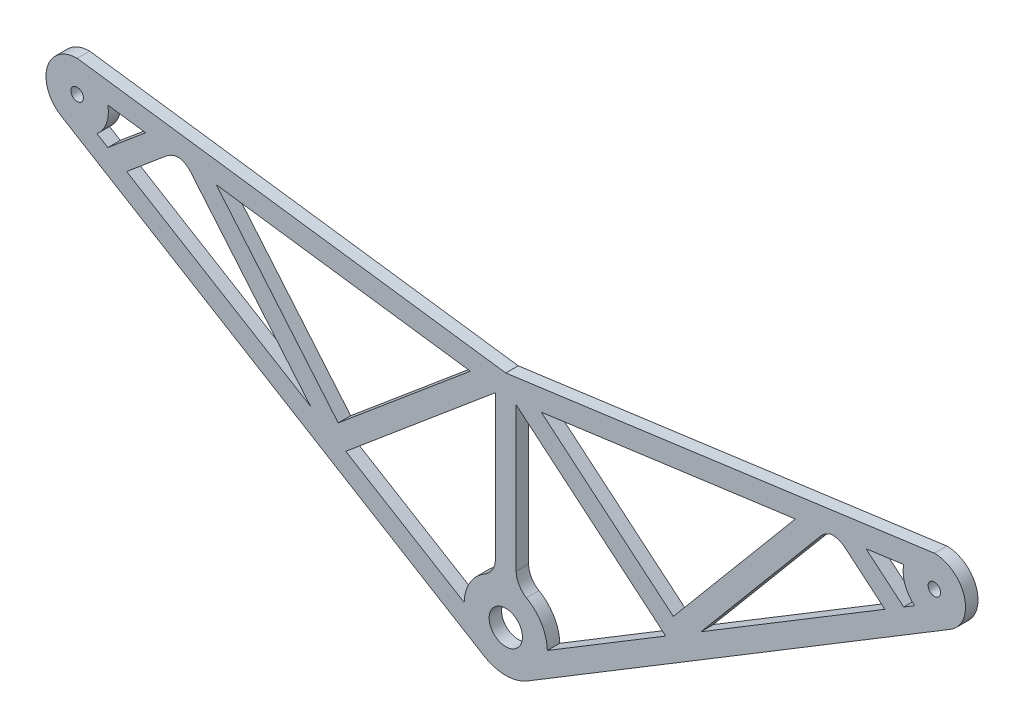
SolidWorks part; units mm, degrees
ref_plane "前视基准面" through (0, 0, 0) normal (0, 0, 1) x (1, 0, 0)
ref_plane "上视基准面" through (0, 0, 0) normal (0, 1, 0) x (1, 0, 0)
ref_plane "右视基准面" through (0, 0, 0) normal (1, 0, 0) x (0, 0, -1)
sketch "草图1" plane through (0, 0, 0) normal (0, 0, 1) x (1, 0, 0)
  line L0 (0, 53) -> (0, -10) construction
  line L1 (0, 0) -> (103.057, 59.5) construction
  line L2 (0, 53) -> (-103.057, 67)
  line L3 (0, 0) -> (-103.057, 59.5) construction
  line L4 (0, 53) -> (103.057, 67)
  line L5 (-106.9426, 53.085) -> (-5.1808, -8.5533)
  line L6 (5.1808, -8.5533) -> (106.9426, 53.085)
  line L7 (0, 53) -> (-40.6004, 18.9323) construction
  line L8 (0, 53) -> (40.6004, 18.9323) construction
  line L9 (-40.6004, 18.9323) -> (-78.0878, 63.608) construction
  line L10 (40.6004, 18.9323) -> (78.0878, 63.608) construction
  line L11 (-78.0878, 63.608) -> (-93.1067, 51.0056) construction
  line L12 (78.0878, 63.608) -> (93.1067, 51.0056) construction
  line L13 (-8.523, 49.1119) -> (-69.6256, 57.4125)
  line L14 (46.9198, 22.5742) -> (91.1632, 49.3729)
  line L15 (-98.3041, 53.6983) -> (-95.6807, 52.1092)
  line L16 (9.9978, 0.2101) -> (38.4702, 17.4562)
  line L17 (-8.523, 49.1119) -> (-40.2922, 22.4543)
  line L18 (-40.2922, 22.4543) -> (-69.6256, 57.4125)
  line L19 (-86.6107, 59.7199) -> (-95.6807, 52.1092)
  line L20 (-2.5, 47.6387) -> (-38.4702, 17.4562)
  line L21 (-46.9198, 22.5742) -> (-76.9924, 58.4133)
  line L22 (-79.916, 58.8104) -> (-91.1632, 49.3729)
  line L23 (2.5, 47.6387) -> (38.4702, 17.4562)
  line L24 (46.9198, 22.5742) -> (76.9924, 58.4133)
  line L25 (79.916, 58.8104) -> (91.1632, 49.3729)
  line L26 (8.523, 49.1119) -> (40.2922, 22.4543)
  line L27 (40.2922, 22.4543) -> (69.6256, 57.4125)
  line L28 (86.6107, 59.7199) -> (95.6807, 52.1092)
  line L29 (-38.4702, 17.4562) -> (-9.9978, 0.2101)
  line L30 (-2.5, 47.6387) -> (-2.5, 9.6825)
  line L31 (2.5, 47.6387) -> (2.5, 9.6825)
  line L32 (77.7796, 67.1301) -> (94.7136, 52.9207) construction
  line L33 (-1.607, 54.9151) -> (-40.2922, 22.4543) construction
  line L34 (1.607, 54.9151) -> (40.2922, 22.4543) construction
  line L35 (1.607, 51.0849) -> (-40.9085, 15.4102) construction
  line L36 (-1.607, 51.0849) -> (40.9085, 15.4102) construction
  line L37 (-2.5, 53) -> (-2.5, -10) construction
  line L38 (2.5, 53) -> (2.5, -10) construction
  line L39 (-40.2922, 22.4543) -> (-77.7796, 67.1301) construction
  line L40 (-77.7796, 67.1301) -> (-94.7136, 52.9207) construction
  line L41 (-40.9085, 15.4102) -> (-78.3959, 60.0859) construction
  line L42 (-78.3959, 60.0859) -> (-91.4997, 49.0905) construction
  line L43 (40.9085, 15.4102) -> (78.3959, 60.0859) construction
  line L44 (2.5, -9.6825) -> (2.5, -10)
  line L45 (40.2922, 22.4543) -> (77.7796, 67.1301) construction
  line L46 (78.3959, 60.0859) -> (91.4997, 49.0905) construction
  line L47 (-2.5, -9.6825) -> (-2.5, -10)
  line L49 (-104.3522, 57.3617) -> (-2.5904, -4.2767) construction
  line L50 (2.5904, -4.2767) -> (104.3522, 57.3617) construction
  line L51 (86.6107, 59.7199) -> (95.6994, 60.9546)
  line L52 (95.6807, 52.1092) -> (98.3041, 53.6983)
  line L53 (76.9924, 58.4133) -> (79.916, 58.8104)
  line L54 (8.523, 49.1119) -> (69.6256, 57.4125)
  line L55 (-76.9924, 58.4133) -> (-79.916, 58.8104)
  line L56 (-86.6107, 59.7199) -> (-95.6994, 60.9546)
  line L57 (-91.1632, 49.3729) -> (-46.9198, 22.5742)
  arc A0 (-2.5, 9.6825) -> (-9.9978, 0.2101) centre (0, 0) ccw
  arc A1 (-98.3041, 53.6983) -> (-95.6994, 60.9546) centre (-103.057, 59.5) ccw
  arc A2 (106.9426, 53.085) -> (101.0562, 66.7282) centre (103.057, 59.5) ccw
  circle A3 centre (0, 0) radius 4
  circle A4 centre (-103.057, 59.5) radius 1.5
  circle A5 centre (103.057, 59.5) radius 1.5
  arc A6 (-5.1808, -8.5533) -> (5.1808, -8.5533) centre (0, 0) ccw
  arc A7 (9.9978, 0.2101) -> (2.5, 9.6825) centre (0, 0) ccw
  arc A8 (95.6994, 60.9546) -> (98.3041, 53.6983) centre (103.057, 59.5) ccw
  arc A9 (-101.0562, 66.7282) -> (-106.9426, 53.085) centre (-103.057, 59.5) ccw
  point P5 (0, 53)
  dimension "D1" = 8
  dimension "D2" = 20
  dimension "D3" = 3
  dimension "D4" = 15
  dimension "D5" = 3
  dimension "D6" = 15
  dimension "D7" = 60
  dimension "D8" = 60
  dimension "D9" = 119
  dimension "D10" = 119
  dimension "D11" = 53
  dimension "D12" = 53
  dimension "D13" = 53
  dimension "D23" = 5
  dimension "D15" = 5
  dimension "D24" = 5
  dimension "D25" = 5
  dimension "D26" = 50
  dimension "D27" = 50
  dimension "D14" = 2.5
  dimension "D16" = 5
  dimension "D17" = 5
  dimension "D18" = 2.5
  dimension "D19" = 2.5
  dimension "D20" = 2.5
  dimension "D21" = 2.5
  dimension "D22" = 2.5
extrude "凸台-拉伸1" add sketch "草图1" along normal blind 3 contours L2 A9 L5 A6 L6 A2 L4 L51 A8 L52 L28 L16 A7 L31 L23 L15 A1 L56 L19 L30 A0 L29 L20 L26 L54 L27 L24 L53 L25 L14 L17 L18 L13 L57 L22 L55 L21 A3
fillet "圆角1" radius 5 2 edges at (76.9924, 58.4133, 1.5) (79.916, 58.8104, 1.5)
fillet "圆角2" radius 5 2 edges at (-79.916, 58.8104, 1.5) (-76.9924, 58.4133, 1.5)
fillet "圆角3" radius 5 2 edges at (2.5, 9.6825, 1.5) (-2.5, 9.6825, 1.5)
